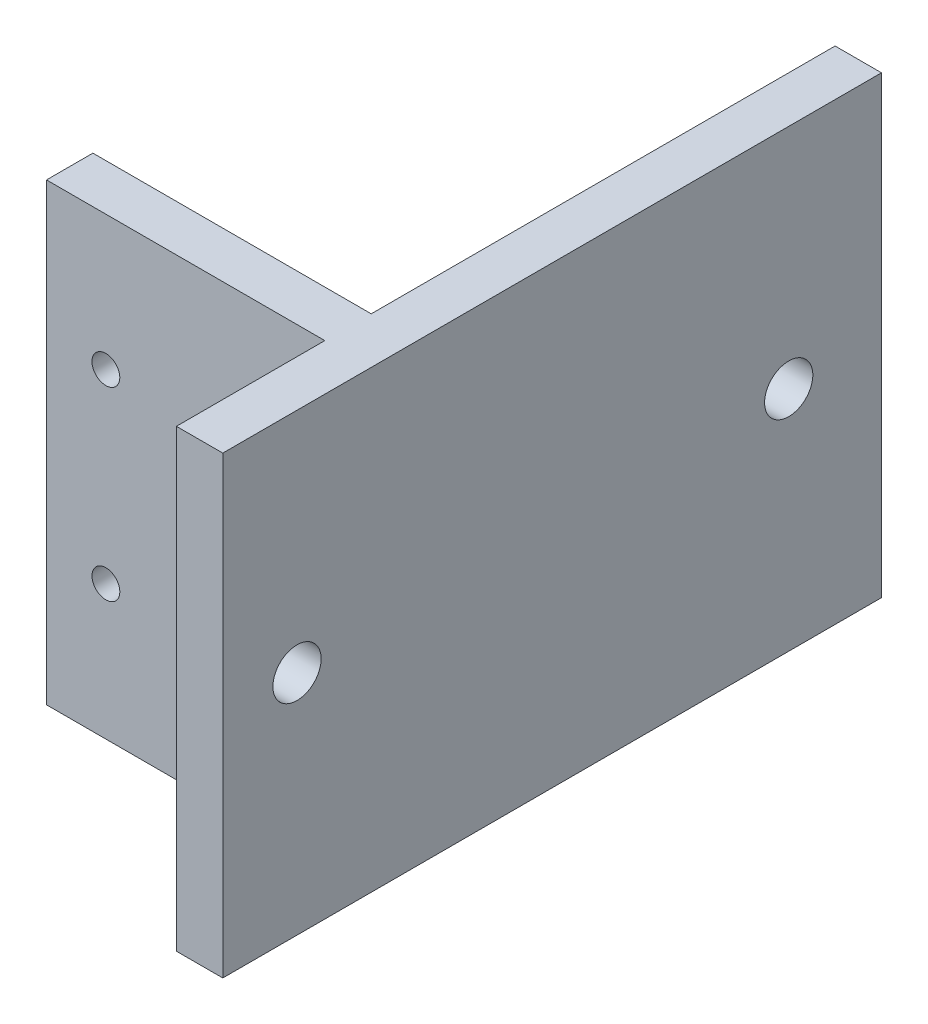
SolidWorks part; units mm, degrees
ref_plane "前视基准面" through (0, 0, 0) normal (0, 0, 1) x (1, 0, 0)
ref_plane "上视基准面" through (0, 0, 0) normal (0, 1, 0) x (1, 0, 0)
ref_plane "右视基准面" through (0, 0, 0) normal (1, 0, 0) x (0, 0, -1)
other "Configuration Table"
sketch "草图1" plane through (0, 0, 0) normal (0, 1, 0) x (1, 0, 0)
  line L0 (30, 0) -> (30, 50)
  line L1 (0, 0) -> (30, 0)
  line L2 (0, 0) -> (0, -5)
  line L3 (0, -5) -> (30, -5)
  line L5 (30, -21) -> (35, -21)
  line L6 (30, -21) -> (30, -5)
  line L7 (30, 50) -> (35, 50)
  line L8 (35, -21) -> (35, 50)
  dimension "D1" = 5
  dimension "D2" = 5
  dimension "D3" = 16
  dimension "D4" = 50
  dimension "D5" = 30
extrude "凸台-拉伸1" add sketch "草图1" along normal blind 49
hole_wizard "孔1" positions "草图2" profile "草图3" legacy end condition through all
sketch "草图2" plane through (0, 0, 5) normal (0, 0, 1) x (1, 0, 0)
  line L0 (30, 49) -> (30, 0) construction
  line L2 (0, 24.5) -> (30, 24.5) construction
  line L3 (0, 49) -> (0, 0) construction
  point P0 (26.4, 34.5)
  point P2 (26.4, 14.5)
  point P4 (6.4, 34.5)
  point P6 (6.4, 14.5)
  dimension "D1" = 3.6
  dimension "D2" = 20
  dimension "D3" = 20
  dimension "D4" = 20
sketch "草图3" plane through (26.4, 34.5, 5) normal (1, 0, 0) x (0, -1, 0)
  line L0 (0, 0) -> (0, 55)
  line L1 (0, 55) -> (1.5, 55)
  line L2 (1.5, 55) -> (1.5, 0)
  line L3 (1.5, 0) -> (0, 0)
  line L4 (0, 110) -> (0, -10) construction
  dimension "直径" = 3
  dimension "深度" = 55
sketch "草图5" plane through (30, 0, 0) normal (-1, 0, 0) x (0, 0, 1)
  line L0 (21, 24.5) -> (5, 24.5) construction
  line L1 (21, 49) -> (21, 0) construction
  line L2 (5, 49) -> (5, 0) construction
  circle A0 centre (13, 24.5) radius 2.6
  dimension "D1" = 5.2
  dimension "D2" = 8
extrude "切除-拉伸1" cut sketch "草图5" against normal blind 10
sketch "草图6" plane through (30, 0, 0) normal (-1, 0, 0) x (0, 0, 1)
  line L0 (0, 24.5) -> (-50, 24.5) construction
  line L1 (0, 49) -> (0, 0) construction
  line L2 (-50, 49) -> (-50, 0) construction
  circle A0 centre (-40, 24.5) radius 2.6
  dimension "D1" = 5.2
  dimension "D2" = 40
extrude "切除-拉伸2" cut sketch "草图6" against normal blind 10
